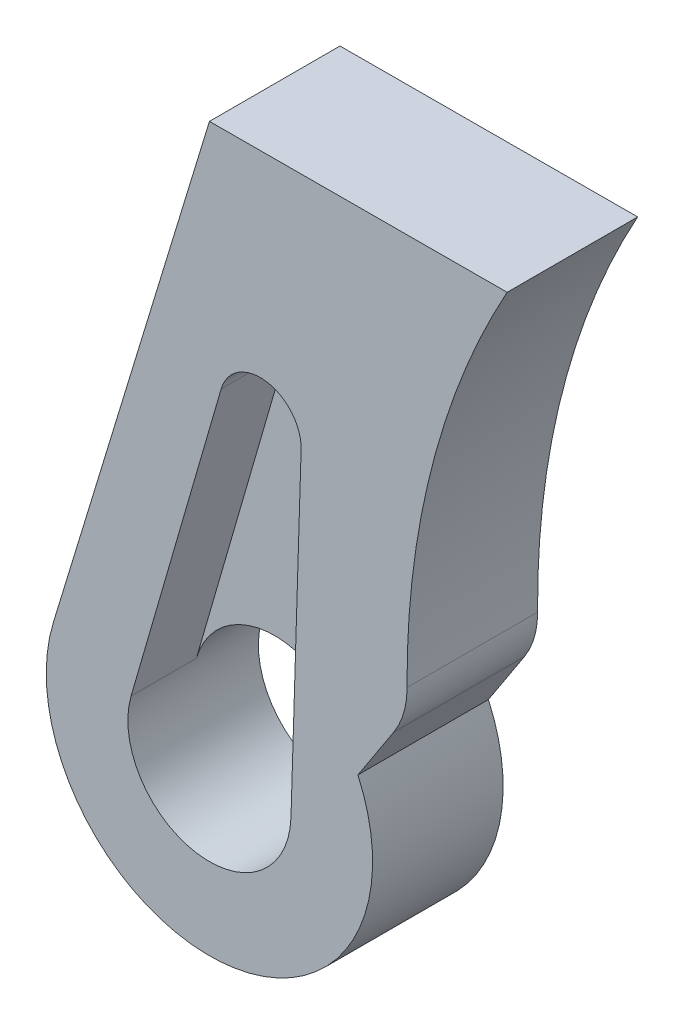
SolidWorks part; units mm, degrees
ref_plane "Front Plane" through (0, 0, 0) normal (0, 0, 1) x (1, 0, 0)
ref_plane "Top Plane" through (0, 0, 0) normal (0, 1, 0) x (1, 0, 0)
ref_plane "Right Plane" through (0, 0, 0) normal (1, 0, 0) x (0, 0, -1)
sketch "Sketch1" plane through (0, 0, 0) normal (0, 0, 1) x (1, 0, 0)
  line L0 (0.625, -4.9608) -> (20.3125, -2.4804) construction
  line L1 (0.625, 4.9608) -> (20.3125, 2.4804) construction
  line L2 (0, 0) -> (20, 0) construction
  line L3 (0, 0) -> (3.12, 19.7551) construction
  line L4 (5.6188, 19.6769) -> (4.9975, -0.1565)
  line L5 (0.7188, 20.4508) -> (-4.8025, 1.3912)
  line L6 (0, 34.2931) -> (18.2476, 34.3446)
  line L7 (12.1472, 8.8253) -> (9.0972, 4.1523)
  line L8 (0, 34.2931) -> (-9.5654, 2.916)
  circle A0 centre (0, 0) radius 5
  circle A1 centre (20, 0) radius 2.5 construction
  circle A2 centre (60.7109, 10.705) radius 48.1 construction
  circle A3 centre (60.7109, 10.705) radius 48.1 construction
  circle A4 centre (3.12, 19.7551) radius 2.5
  circle A5 centre (60.7109, 10.705) radius 48.6
  circle A6 centre (0, 0) radius 10
  point P22 (25.3193, 0)
  point P27 (30.834, -5.0903)
  point P28 (25.6829, 0)
  point P29 (31.8365, -0.5588)
  point P32 (19.2007, -4.9608)
  point P33 (33.5503, -0.652)
  point P34 (37.8502, -10.5284)
  point P35 (11.5211, -14.0214)
  point P36 (6.4661, -7.6282)
  point P37 (36.425, 8.5055)
  point P38 (20, 1.6895)
  point P39 (31.1063, 8.3002)
  point P40 (11.2784, -8.5604)
  point P41 (13.8332, -7.5755)
  point P42 (3.6755, 28.9625)
  point P43 (15.4319, 29.4431)
  point P44 (6.9717, 18.7455)
  point P45 (4.9608, 19.3748)
  point P46 (12.1472, 8.8253)
  point P47 (0, 34.2931)
  point P48 (18.2476, 34.2931)
  point P49 (3.12, 19.6769)
  point P50 (9.0972, 4.1523)
  dimension "D1" = 10
  dimension "D2" = 5
  dimension "D5" = 20
  dimension "D3" = 20
  dimension "D4" = 0.5
extrude "Boss-Extrude1" add sketch "Sketch1" along normal blind 8 contours L5 A6 L4 A0 | L4 A6 L5 A0 | A6 L5 A4 L4 L7 A5 L6 L8 | A6 L4 A4 L5 | A4 region at (5.5683, 22.0415, 0) region at (2.1428, 13.5675, 0) region at (3.12, 19.7551, 0) region at (7.2939, 6.4236, 0) region at (1.0555, 6.6829, 0)
extrude "Cut-Extrude1" cut sketch "Sketch1<3>" against normal blind 4 from surface contours A4 | A6 L4 A4 L5 | L4 A6 L5 A0 region at (2.1428, 13.5675, 0) region at (3.12, 19.7551, 0) region at (1.0555, 6.6829, 0) starting at face at (5.8134, 14.2877, 8)
sketch "Sketch1<3>" plane through (0, 0, 0) normal (0, 0, 1) x (1, 0, 0) same geometry as "Sketch1"
fillet "Fillet1" radius 5 1 edges at (12.1472, 8.8253, 4)
